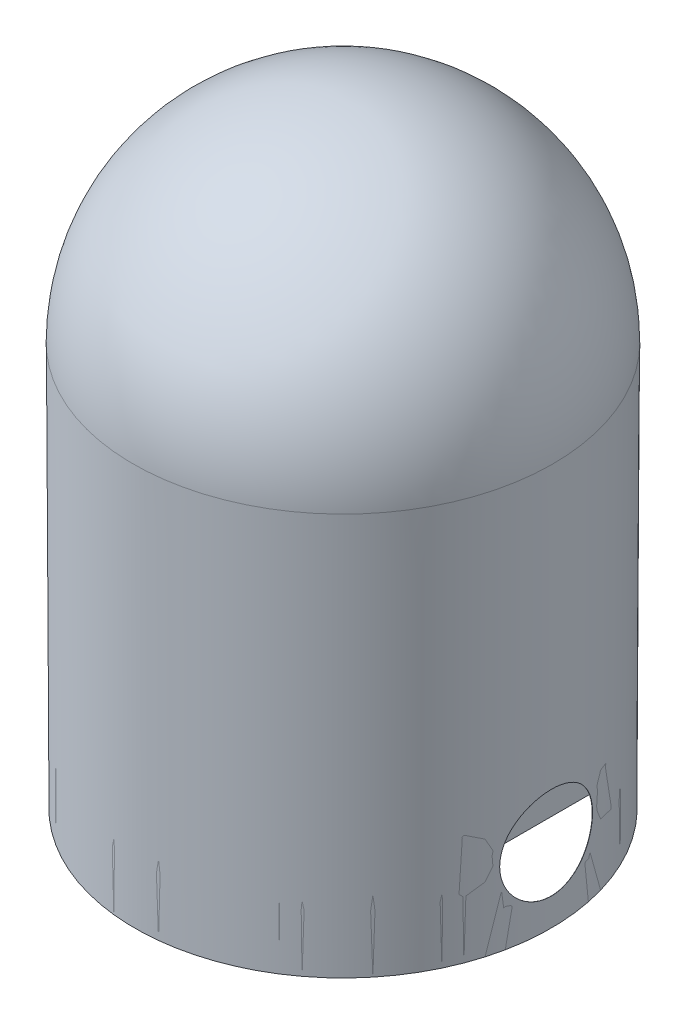
SolidWorks part; units mm, degrees
ref_plane "Front Plane" through (0, 0, 0) normal (0, 0, 1) x (1, 0, 0)
ref_plane "Top Plane" through (0, 0, 0) normal (0, 1, 0) x (1, 0, 0)
ref_plane "Right Plane" through (0, 0, 0) normal (1, 0, 0) x (0, 0, -1)
sketch "Sketch1" plane through (0, 0, 0) normal (0, 0, 1) x (1, 0, 0)
  line L0 (0, 0) -> (0, 5.6026)
  line L1 (0, 0) -> (-14.224, 0)
  line L2 (-14.224, 0) -> (-14.351, 27.559)
  line L6 (0, 5.6026) -> (-2.54, 5.6026)
  line L7 (-2.54, 22.86) -> (-2.54, 5.6026)
  line L8 (0, 32.9006) -> (0, 41.91)
  arc A0 (0, 41.91) -> (-14.351, 27.559) centre (0, 27.559) ccw
  arc A1 (-2.54, 22.86) -> (0, 32.9006) centre (0, 27.559) cw
  dimension "D3" = 28.702
  dimension "D1" = 41.91
  dimension "D2" = 14.224
  dimension "D4" = 2.54
revolve "Revolve1" add sketch "Sketch1" angle 360 about L0
sketch "Sketch2" plane through (0, 0, 0) normal (0, -1, 0) x (1, 0, 0)
  line L0 (-2.54, 13.9954) -> (-2.54, -13.9954)
  line L1 (-7.62, 12.0107) -> (-7.62, -12.0107)
  line L2 (2.54, 13.9954) -> (2.54, -13.9954)
  line L3 (7.62, 12.0107) -> (7.62, -12.0107)
  circle A0 centre (0, 0) radius 14.224 construction
  arc A1 (-7.62, 12.0107) -> (-7.62, -12.0107) centre (0, 0) ccw
  arc A2 (-2.54, -13.9954) -> (2.54, -13.9954) centre (0, 0) ccw
  arc A3 (7.62, -12.0107) -> (7.62, 12.0107) centre (0, 0) ccw
  arc A4 (2.54, 13.9954) -> (-2.54, 13.9954) centre (0, 0) ccw
  dimension "D1" = 2.54
  dimension "D2" = 5.08
  dimension "D3" = 2.54
  dimension "D4" = 5.08
extrude "Cut-Extrude1" cut sketch "Sketch2" against normal blind 10.16
sketch "Sketch3" plane through (-7.62, 0, 0) normal (-1, 0, 0) x (0, 0, 1)
  line L0 (0, -13.97) -> (0, 13.97) construction
  line L1 (-12.0107, 0) -> (12.0107, 0) construction
  circle A0 centre (0, 5.08) radius 3.175
  dimension "D2" = 6.35
  dimension "D1" = 5.08
extrude "Cut-Extrude2" cut sketch "Sketch3" against normal through all
fillet "Fillet1" radius 2.54 rebuild error yes
